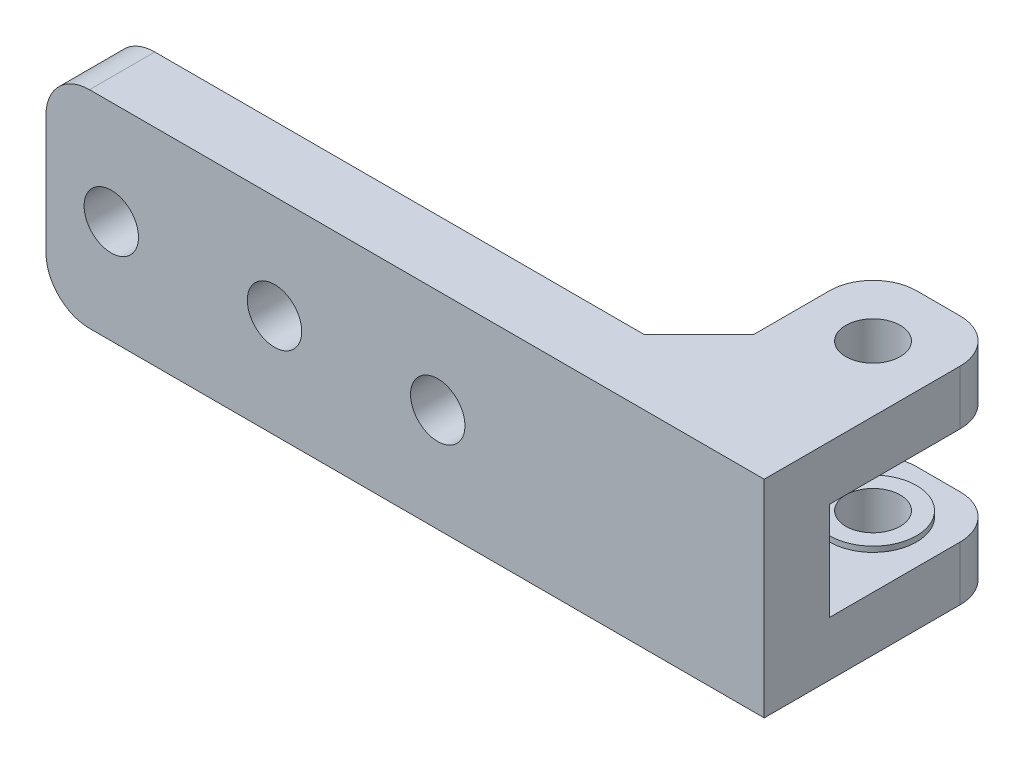
SolidWorks part; units mm, degrees
ref_plane "Спереди" through (0, 0, 0) normal (0, 0, 1) x (1, 0, 0)
ref_plane "Сверху" through (0, 0, 0) normal (0, 1, 0) x (1, 0, 0)
ref_plane "Справа" through (0, 0, 0) normal (1, 0, 0) x (0, 0, -1)
sketch "Эскиз1" plane through (0, 0, 0) normal (1, 0, 0) x (0, 0, -1)
  line L0 (0, 0) -> (22, 0)
  line L1 (22, 0) -> (22, 5)
  line L2 (22, 5) -> (6, 5)
  line L3 (6, 5) -> (6, 14)
  line L4 (6, 14) -> (22, 14)
  line L5 (22, 14) -> (22, 19)
  line L6 (22, 19) -> (0, 19)
  line L7 (0, 19) -> (0, 0)
  point P3 (14.5492, 0)
  point P11 (0, -0.0886)
  dimension "D1" = 9
  dimension "D2" = 5
  dimension "D3" = 16
  dimension "D4" = 22
extrude "Бобышка-Вытянуть1" add sketch "Эскиз1" along normal blind 12
sketch "Эскиз2" plane through (0, 19, 0) normal (0, 1, 0) x (1, 0, 0)
  line L0 (6, 22) -> (6, 0) construction
  line L1 (12, 22) -> (0, 22) construction
  line L2 (12, 0) -> (0, 0) construction
  circle A0 centre (6, 16) radius 2.5
  dimension "D1" = 5
  dimension "D2" = 6
extrude "Вырез-Вытянуть1" cut sketch "Эскиз2" against normal through all
sketch "Эскиз3" plane through (0, 14, 0) normal (0, -1, 0) x (1, 0, 0)
  circle A0 centre (6, -16) radius 2.5
  circle A1 centre (6, -16) radius 4
  dimension "D1" = 8
  dimension "D2" = 5
extrude "Бобышка-Вытянуть2" add sketch "Эскиз3" along normal blind 0.5
sketch "Эскиз4" plane through (0, 5, 0) normal (0, 1, 0) x (1, 0, 0)
  circle A0 centre (6, 16) radius 2.5
  circle A1 centre (6, 16) radius 4
  dimension "D1" = 8
  dimension "D2" = 5
extrude "Бобышка-Вытянуть3" add sketch "Эскиз4" along normal blind 0.5
fillet "Скругление1" radius 4 4 edges at (0, 16.5, -22) (0, 2.5, -22) (12, 2.5, -22) (12, 16.5, -22)
sketch "Эскиз5" plane through (0, 0, 0) normal (0, 0, 1) x (1, 0, 0)
  line L1 (0, 19) -> (-54, 19)
  line L2 (0, 19) -> (0, 0)
  line L3 (0, 0) -> (-54, 0)
  line L4 (-54, 19) -> (-54, 0)
  point P5 (0, 0)
  dimension "D1" = 54
extrude "Бобышка-Вытянуть4" add sketch "Эскиз5" against normal up to vertex (6 mm away) up to point (0, 5, -6)
chamfer "Фаска1" distance 5 angle 45 2 edges at (0, 2.5, -6) (0, 16.5, -6)
sketch "Эскиз6" plane through (0, 0, -6) normal (0, 0, -1) x (-1, 0, 0)
  line L0 (-12, 9.5) -> (54, 9.5) construction
  line L1 (-12, 5) -> (-12, 14) construction
  line L2 (54, 19) -> (54, 0) construction
  circle A0 centre (48, 9.5) radius 2.5
  circle A1 centre (33, 9.5) radius 2.5
  circle A2 centre (18, 9.5) radius 2.5
  dimension "D1" = 5
  dimension "D2" = 6
  dimension "D3" = 15
  dimension "D4" = 15
extrude "Вырез-Вытянуть2" cut sketch "Эскиз6" against normal through all
fillet "Скругление2" radius 4 2 edges at (-54, 0, -3) (-54, 19, -3)
